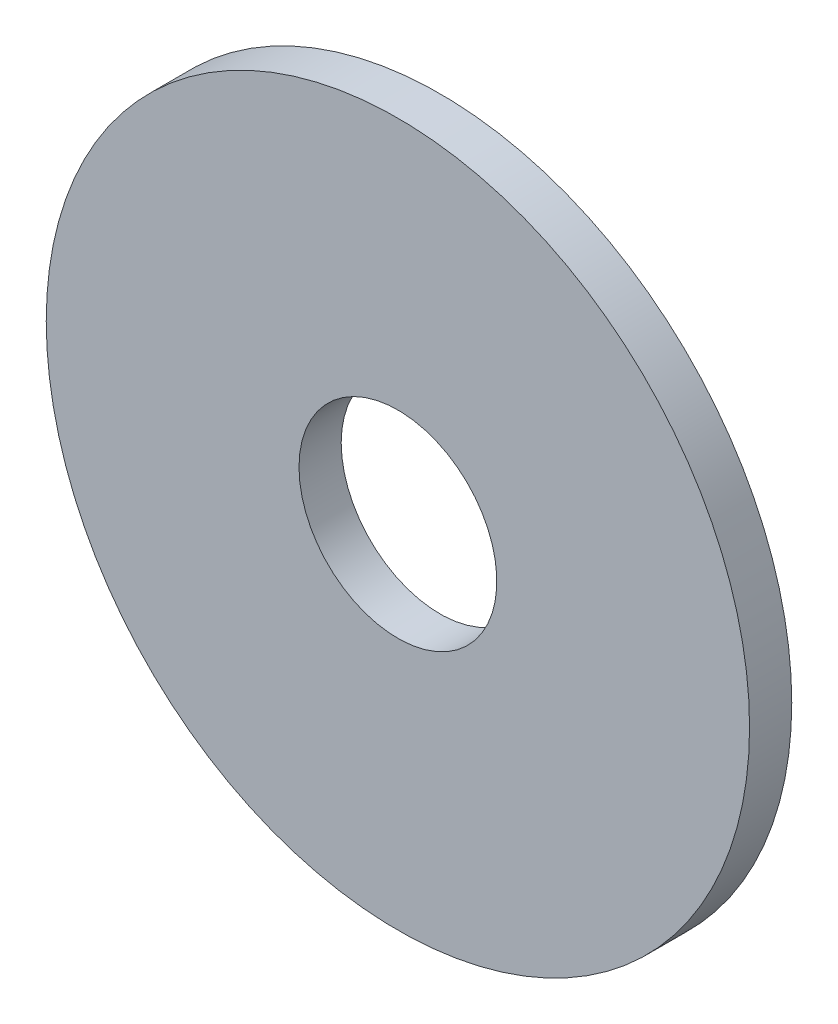
SolidWorks part; units mm, degrees
material "Alloy Steel"
ref_plane "Front Plane" through (0, 0, 0) normal (0, 0, 1) x (1, 0, 0)
ref_plane "Top Plane" through (0, 0, 0) normal (0, 1, 0) x (1, 0, 0)
ref_plane "Right Plane" through (0, 0, 0) normal (1, 0, 0) x (0, 0, -1)
ref_axis "Axis1" through (0, 0, -12.737) along (0, 0, 1)
ref_axis "Axis2" through (0, -40.0342, 0) along (0, 1, 0)
ref_axis "Axis3" through (-41.1327, 0, 0) along (1, 0, 0)
sketch "Sketch1" plane through (0, 0, 0) normal (0, 0, 1) x (1, 0, 0)
  circle A0 centre (0, 0) radius 12.7
  circle A1 centre (0, 0) radius 3.5719
  dimension "OD" = 25.4
  dimension "ID" = 7.1437
extrude "Boss-Extrude1" add sketch "Sketch1" along normal mid plane 1.524
